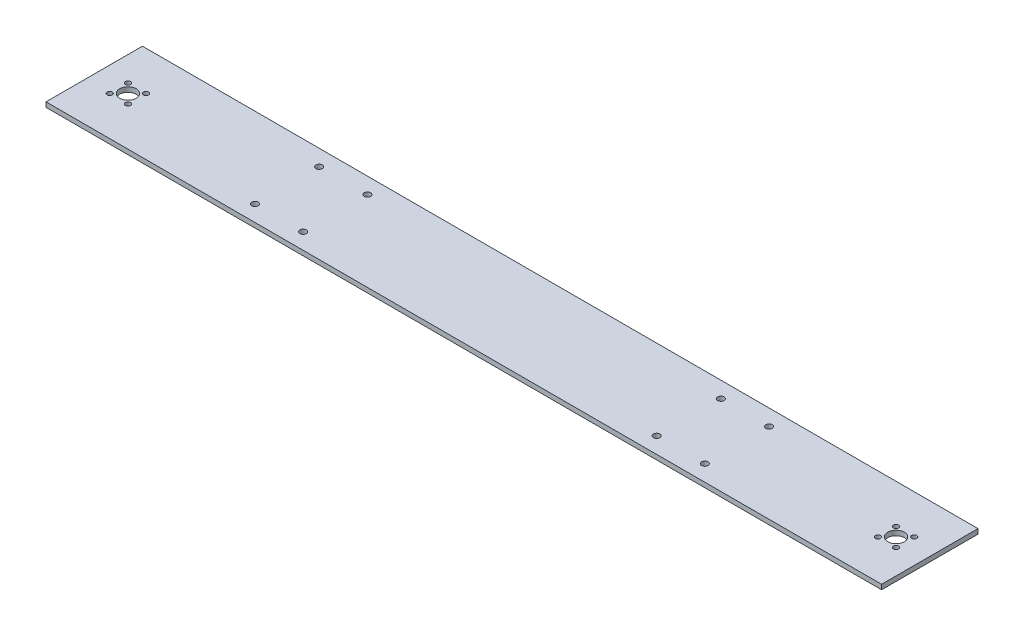
SolidWorks part; units mm, degrees
material "3.0515 (EN-AW 3103)"
ref_plane "Płaszczyzna przednia" through (0, 0, 0) normal (0, 0, 1) x (1, 0, 0)
ref_plane "Płaszczyzna górna" through (0, 0, 0) normal (0, 1, 0) x (1, 0, 0)
ref_plane "Płaszczyzna prawa" through (0, 0, 0) normal (1, 0, 0) x (0, 0, -1)
sketch "Szkic1" plane through (0, 0, 0) normal (0, 1, 0) x (1, 0, 0)
  line L1 (0, 0) -> (-520, 0)
  line L2 (0, 0) -> (0, 60)
  line L3 (0, 60) -> (-520, 60)
  line L4 (-520, 0) -> (-520, 60)
  dimension "D1" = 60
  dimension "D2" = 520
extrude "Dodanie-wyciągnięcie1" add sketch "Szkic1" along normal blind 3
hole_wizard "Otwór pod śrubę M41" positions "Szkic6" profile "Szkic7" hole size "M4" standard "Ansi Metric" end condition through all
sketch "Szkic6" plane through (0, 3, 0) normal (0, 1, 0) x (1, 0, 0)
  line L0 (0, 60) -> (-520, 60) construction
  line L1 (-520, 0) -> (0, 0) construction
  line L2 (-520, 60) -> (-520, 0) construction
  line L3 (0, 0) -> (0, 60) construction
  point P0 (-400, 50)
  point P2 (-370, 50)
  point P4 (-400, 10)
  point P6 (-370, 10)
  point P8 (-150, 50)
  point P10 (-120, 50)
  point P12 (-150, 10)
  point P14 (-120, 10)
  dimension "D1" = 10
  dimension "D2" = 10
  dimension "D3" = 30
  dimension "D4" = 30
  dimension "D5" = 30
  dimension "D6" = 30
  dimension "D7" = 120
  dimension "D8" = 120
  dimension "D9" = 120
  dimension "D10" = 120
sketch "Szkic7" plane through (-400, 3, -50) normal (1, 0, 0) x (0, 0, 1)
  line L0 (0, 0) -> (0, 3)
  line L1 (0, 3) -> (2, 3)
  line L2 (2, 3) -> (2, 0)
  line L5 (2, 0) -> (0, 0)
  line L11 (0, -6.35) -> (0, 107.95) construction
  dimension "Œrednica otworu na wylot" = 4
  dimension "G³êbokoœæ otworu na wylot" = 3
sketch "Szkic8" plane through (0, 3, 0) normal (0, 1, 0) x (1, 0, 0)
  line L0 (0, 60) -> (-520, 60) construction
  line L2 (0, 0) -> (0, 60) construction
  line L3 (-520, 60) -> (-520, 0) construction
  circle A0 centre (-21, 30) radius 5.15
  circle A1 centre (-499, 30) radius 5.15
  dimension "D1" = 10.3
  dimension "D2" = 30
  dimension "D3" = 21
  dimension "D4" = 10.3
  dimension "D5" = 30
  dimension "D6" = 21
extrude "Wytnij-wyciągnięcie1" cut sketch "Szkic8" against normal blind 10
sketch "Szkic9" plane through (0, 3, 0) normal (0, 1, 0) x (1, 0, 0)
  circle A4 centre (-504.65, 35.6637) radius 1.6
  circle A5 centre (-499, 30) radius 5.15 construction
  circle A6 centre (-493.3363, 35.65) radius 1.6
  circle A7 centre (-493.35, 24.3363) radius 1.6
  circle A8 centre (-504.6637, 24.35) radius 1.6
  dimension "D1" = 3.2
  dimension "D2" = 8
  dimension "D3" = 5.65
  dimension "D4" = 4
extrude "Wytnij-wyciągnięcie2" cut sketch "Szkic9" against normal through all
sketch "Szkic10" plane through (0, 3, 0) normal (0, 1, 0) x (1, 0, 0)
  circle A0 centre (-15.35, 35.6637) radius 1.6
  circle A5 centre (-21, 30) radius 5.15 construction
  circle A6 centre (-15.3363, 24.35) radius 1.6
  circle A7 centre (-26.65, 24.3363) radius 1.6
  circle A8 centre (-26.6637, 35.65) radius 1.6
  dimension "D1" = 3.2
  dimension "D2" = 8
  dimension "D3" = 5.65
  dimension "D4" = 5.6637
  dimension "D5" = 4
extrude "Wytnij-wyciągnięcie3" cut sketch "Szkic10" against normal blind 10
ref_plane "Plane1" through (-295, 0, 0) normal (1, 0, 0) x (0, 0, -1)
